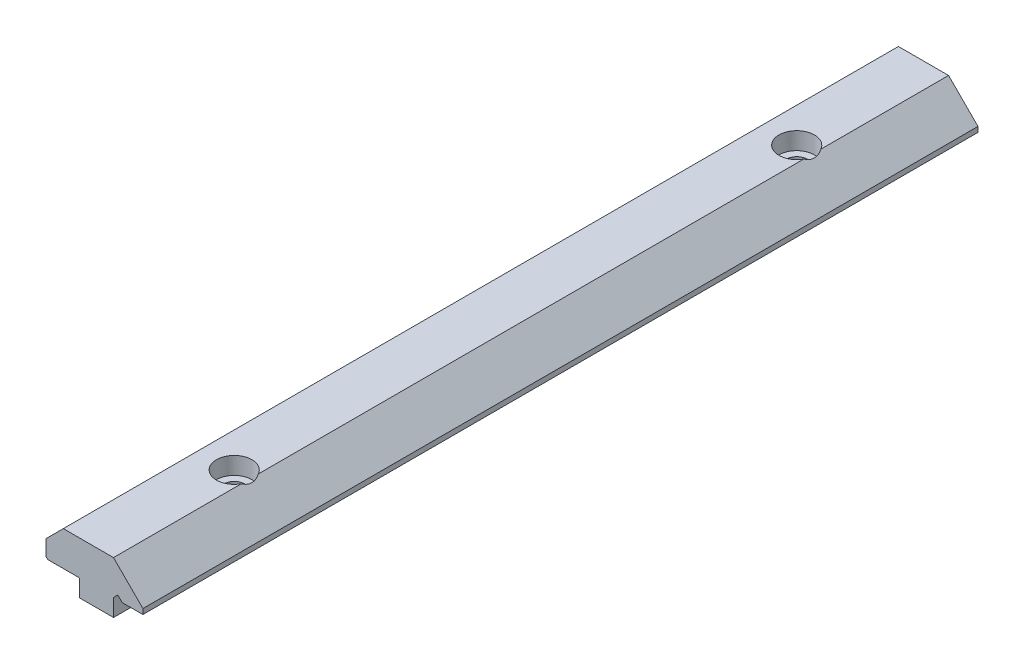
SolidWorks part; units mm, degrees
ref_plane "前视基准面" through (0, 0, 0) normal (0, 0, 1) x (1, 0, 0)
ref_plane "上视基准面" through (0, 0, 0) normal (0, 1, 0) x (1, 0, 0)
ref_plane "右视基准面" through (0, 0, 0) normal (1, 0, 0) x (0, 0, -1)
sketch "草图1" plane through (0, 0, 0) normal (0, 0, 1) x (1, 0, 0)
  line L1 (0, 0) -> (7, 0)
  line L3 (0, 4) -> (7, 4)
  line L4 (7, 0) -> (7, 4)
  line L5 (0, 4) -> (-1.8, 4)
  line L6 (0, 0) -> (0, -1.9)
  line L7 (0, -1.9) -> (-1.8, -1.9)
  line L8 (-1.8, 4) -> (-1.8, -1.9)
  dimension "D1" = 1.8
  dimension "D2" = 1.9
  dimension "D3" = 4
  dimension "D4" = 7
extrude "凸台-拉伸1" add sketch "草图1" against normal blind 96.5
chamfer "倒角1" distance 1 angle 45 1 edges at (7, 0, -48.25)
chamfer "倒角2" distance 1 angle 45 1 edges at (7, 4, -48.25)
sketch "草图2" plane through (0, 4, 0) normal (0, 1, 0) x (1, 0, 0)
  line L0 (4.2, 105.0677) -> (4.2, -16.3861) construction
  line L1 (-1.8, 96.5) -> (-1.8, 0) construction
  line L4 (-28.4042, 48.25) -> (44.7588, 48.25) construction
  line L9 (-1.8, 0) -> (6, 0)
  line L10 (6, 0) -> (6, 96.5)
  line L11 (6, 96.5) -> (-1.8, 96.5)
  line L12 (-1.8, 96.5) -> (-1.8, 0)
  line L13 (-1.8, 0) -> (6, 0) construction
  line L15 (6, 96.5) -> (-1.8, 96.5) construction
  circle A1 centre (4.2, 80.75) radius 2.05
  circle A3 centre (4.2, 15.75) radius 2.05
  circle A4 centre (4.2, 80.75) radius 1.2
  circle A7 centre (4.2, 15.75) radius 1.2
  dimension "D3" = 65
  dimension "D5" = 4.1
  dimension "D6" = 2.4
  dimension "D1" = 0
  dimension "D2" = 6
extrude "切除-拉伸1" cut sketch "草图2" against normal blind 10 and the other way through all contours A7 | A4
extrude "切除-拉伸2" cut sketch "草图2<3>" against normal blind 2 contours A1 | A3
sketch "草图2<3>" plane through (0, 4, 0) normal (0, 1, 0) x (1, 0, 0) same geometry as "草图2"
chamfer "倒角3" distance 2 angle 45 1 edges at (-1.8, 4, -48.25)
sketch "草图3" plane through (0, -1.9, 0) normal (0, -1, 0) x (1, 0, 0)
  line L0 (0, -96.5) -> (0, 0) construction
  line L1 (-1.8, -96.5) -> (0, -96.5)
  line L2 (-1.8, -96.5) -> (-1.8, -89.1)
  line L3 (-1.8, -89.1) -> (0, -89.1)
  line L4 (0, -96.5) -> (0, -89.1)
  line L5 (-1.8, 0) -> (0, 0)
  line L6 (-1.8, 0) -> (-1.8, -7.4)
  line L7 (-1.8, -7.4) -> (0, -7.4)
  line L8 (0, 0) -> (0, -7.4)
  dimension "D1" = 7.4
extrude "切除-拉伸3" cut sketch "草图3" against normal up to surface (1.9 mm away) up to face at (4.2, 0, -16.95)
chamfer "倒角4" distance 0.2 angle 45 8 edges at (0, -0.95, -89.1) (0, -0.95, -7.4) (0, -1.9, -48.25) (-1.8, 0, -92.8) (-1.8, -0.95, -89.1) (-1.8, 0, -3.7) (-1.8, -0.95, -7.4) (-1.8, -1.9, -48.25)
chamfer "倒角5" distance 0.6 angle 45 2 edges at (-0.9, -1.9, -89.1) (-0.9, -1.9, -7.4)
sketch "草图4" plane through (0, 0, 0) normal (0, -1, 0) x (1, 0, 0)
  line L1 (6, -96.5) -> (2.1, -96.5)
  line L2 (6, -96.5) -> (6, -88.6)
  line L3 (6, -88.6) -> (2.1, -88.6)
  line L4 (2.1, -96.5) -> (2.1, -88.6)
  line L5 (6, 0) -> (2.1, 0)
  line L6 (6, 0) -> (6, -7.9)
  line L7 (6, -7.9) -> (2.1, -7.9)
  line L8 (2.1, 0) -> (2.1, -7.9)
  dimension "D1" = 3.9
  dimension "D2" = 7.9
extrude "凸台-拉伸2" add sketch "草图4" along normal blind 2
chamfer "倒角6" distance 0.4 angle 45 2 edges at (6, -1, -7.9) (6, -1, -88.6)
sketch "草图5" plane through (0, 0, 0) normal (0, 0, 1) x (1, 0, 0)
  line L0 (7, 3) -> (9.4, 0.6)
  line L1 (7, 0) -> (9.4, 0)
  line L2 (6.5, 0.5) -> (7, 0)
  line L3 (6, 0) -> (7, 1) construction
  line L4 (7, 1) -> (7, 3) construction
  line L5 (7, 1) -> (7, 3)
  line L6 (6.5, 0.5) -> (7, 1)
  line L7 (7, 3) -> (6, 4) construction
  line L9 (9.4, 0.6) -> (9.4, 0)
  dimension "D1" = 0.6
extrude "凸台-拉伸3" add sketch "草图5" against normal up to surface (96.5 mm away) up to face at (2.8364, 0.9273, -96.5)
